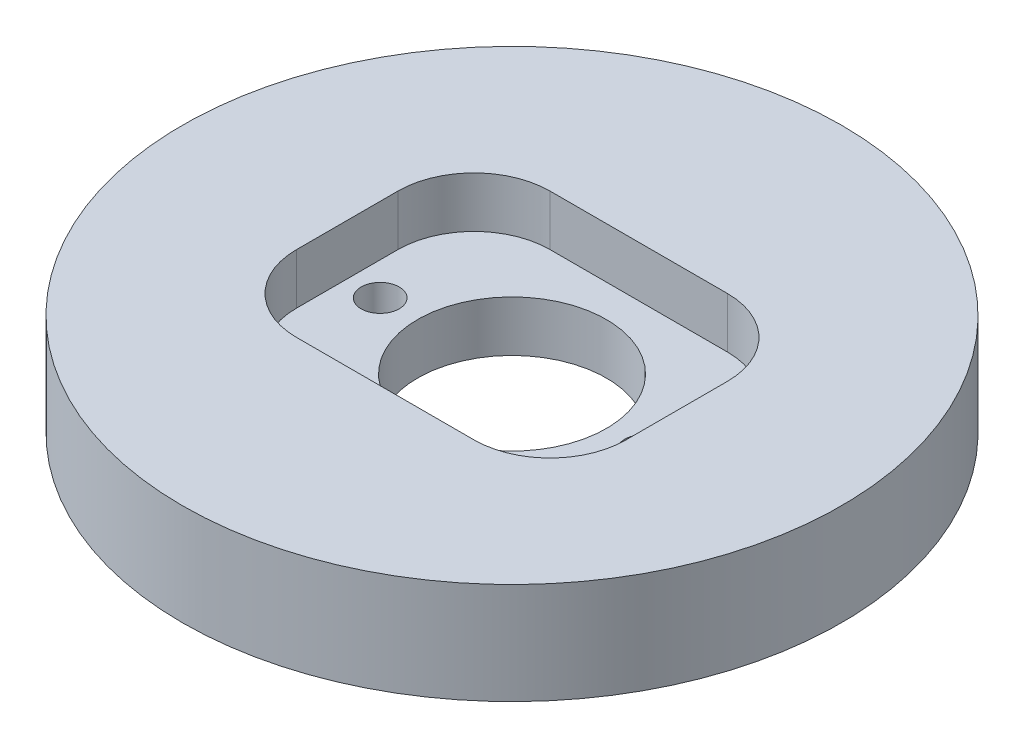
SolidWorks part; units mm, degrees
ref_plane "Front Plane" through (0, 0, 0) normal (0, 0, 1) x (1, 0, 0)
ref_plane "Top Plane" through (0, 0, 0) normal (0, 1, 0) x (1, 0, 0)
ref_plane "Right Plane" through (0, 0, 0) normal (1, 0, 0) x (0, 0, -1)
sketch "Sketch2" plane through (0, 0, 0) normal (0, 1, 0) x (1, 0, 0)
  line L0 (0, 13) -> (0, -22.3339) construction
  line L1 (13, 0) -> (-25.2541, 0) construction
  circle A0 centre (0, 0) radius 13
  dimension "D1" = 26
extrude "Boss-Extrude1" add sketch "Sketch2" along normal blind 4
sketch "Sketch3" plane through (0, 4, 0) normal (0, 1, 0) x (1, 0, 0)
  line L1 (-6.5, 5) -> (6.5, 5)
  line L2 (-6.5, 5) -> (-6.5, -5)
  line L3 (-6.5, -5) -> (6.5, -5)
  line L4 (6.5, 5) -> (6.5, -5)
  line L5 (-6.5, 5) -> (6.5, -5) construction
  line L6 (-6.5, -5) -> (6.5, 5) construction
  point P0 (0, 0)
  point P5 (0, 0)
  point P6 (0, 0)
  dimension "D1" = 13
  dimension "D2" = 10
extrude "Cut-Extrude1" cut sketch "Sketch3" against normal blind 2
fillet "Fillet1" radius 3 4 edges at (-6.5, 3, 5) (6.5, 3, 5) (-6.5, 3, -5) (6.5, 3, -5)
sketch "Sketch4" plane through (0, 2, 0) normal (0, 1, 0) x (1, 0, 0)
  line L1 (3.5, 5) -> (-3.5, 5) construction
  line L2 (0, 0) -> (0, -18.2909) construction
  circle A0 centre (0, 0) radius 3.725
  circle A2 centre (-5.2, 0) radius 0.75
  circle A3 centre (5.2, 0) radius 0.75
  dimension "D1" = 7.45
  dimension "D2" = 5.2
  dimension "D3" = 5
extrude "Cut-Extrude2" cut sketch "Sketch4" against normal through all
